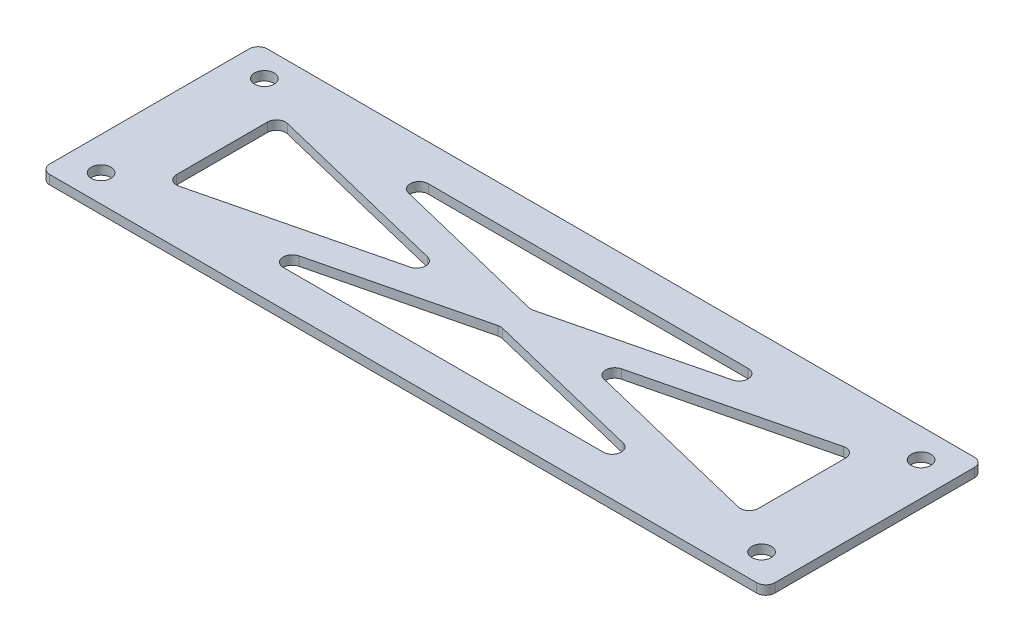
SolidWorks part; units mm, degrees
ref_plane "Front Plane" through (0, 0, 0) normal (0, 0, 1) x (1, 0, 0)
ref_plane "Top Plane" through (0, 0, 0) normal (0, 1, 0) x (1, 0, 0)
ref_plane "Right Plane" through (0, 0, 0) normal (1, 0, 0) x (0, 0, -1)
sketch "Sketch1" plane through (0, 0, 0) normal (0, 1, 0) x (1, 0, 0)
  line L0 (-115.35, 0) -> (115.35, 0) construction
  line L1 (-127, -38.1) -> (127, -38.1)
  line L2 (-127, -38.1) -> (-127, 38.1)
  line L3 (-127, 38.1) -> (127, 38.1)
  line L4 (127, -38.1) -> (127, 38.1)
  line L5 (-127, -38.1) -> (127, 38.1) construction
  line L6 (-127, 38.1) -> (127, -38.1) construction
  line L7 (-115.35, 28.575) -> (-115.35, -28.575) construction
  line L8 (115.35, 27.94) -> (115.35, -27.94) construction
  circle A3 centre (-115.35, 28.575) radius 3.429
  circle A4 centre (-115.35, -28.575) radius 3.429
  circle A5 centre (115.35, 27.94) radius 3.429
  circle A6 centre (115.35, -27.94) radius 3.429
  point P0 (0, 0)
  point P8 (0, 0)
  point P13 (-115.35, 0)
  point P18 (115.35, 0)
  point P21 (0, 0)
  dimension "D4" = 57.15
  dimension "D5" = 6.858
  dimension "D1" = 254
  dimension "D2" = 76.2
  dimension "D3" = 230.7
  dimension "D6" = 55.88
extrude "Boss-Extrude1" add sketch "Sketch1" along normal blind 3.175
fillet "Fillet1" radius 3.175 4 edges at (127, 1.5875, -38.1) (127, 1.5875, 38.1) (-127, 1.5875, -38.1) (-127, 1.5875, 38.1)
sketch "Sketch2" plane through (0, 3.175, 0) normal (0, 1, 0) x (1, 0, 0)
  line L0 (-101.6, 25.4) -> (-101.6, -25.4)
  line L1 (101.6, -25.4) -> (101.6, 25.4)
  line L12 (-115.35, 28.575) -> (115.35, -27.94) construction
  line L13 (-115.35, -28.575) -> (115.35, 27.94) construction
  line L14 (-116.5587, 23.6409) -> (114.1413, -32.8741)
  line L15 (-114.1413, -33.5091) -> (116.5587, 23.0059)
  line L16 (-114.3, 25.4) -> (-114.3, -25.4)
  line L17 (-114.3, -25.4) -> (114.3, -25.4)
  line L18 (114.3, -25.4) -> (114.3, 25.4)
  line L19 (114.3, 25.4) -> (-114.3, 25.4)
  line L20 (-114.3, 25.4) -> (-114.3, -25.4)
  line L21 (-114.3, -25.4) -> (114.3, -25.4)
  line L22 (114.3, -25.4) -> (114.3, 25.4)
  line L23 (114.3, 25.4) -> (-114.3, 25.4)
  line L24 (-114.1413, 33.5091) -> (116.5587, -23.0059)
  line L25 (-116.5587, -23.6409) -> (114.1413, 32.8741)
  circle A18 centre (-115.35, 28.575) radius 16.129
  circle A19 centre (-115.35, 28.575) radius 16.129
  circle A24 centre (115.35, 27.94) radius 16.129
  circle A25 centre (115.35, 27.94) radius 16.129
  circle A27 centre (115.35, -27.94) radius 16.129
  circle A28 centre (115.35, -27.94) radius 16.129
  circle A30 centre (-115.35, -28.575) radius 16.129
  circle A31 centre (-115.35, -28.575) radius 16.129
  dimension "D7" = 5.08
  dimension "D1" = 12.7
  dimension "D2" = 12.7
  dimension "D4" = 12.7
  dimension "D5" = 12.7
  dimension "D6" = 12.7
  dimension "D8" = 5.08
  dimension "D9" = 12.7
extrude "Cut-Extrude1" cut sketch "Sketch2" against normal through all contours L0 L25 L14 | L25 L23 L24 | L15 L24 L1 | L15 L21 L14 region at (-74.4181, 3.175, 0) region at (1.2961, 3.175, -18.6767) region at (1.2961, 3.175, 18.6767) region at (75.2821, 3.175, 0)
fillet "Fillet3" radius 3.175 12 edges at (22.6463, 1.5875, 0) (83.6312, 1.5875, -25.4) (83.6312, 1.5875, 25.4) (-81.0391, 1.5875, 25.4) (-81.0391, 1.5875, -25.4) (-20.0542, 1.5875, 0) (101.6, 1.5875, -19.3414) (101.6, 1.5875, 19.3414) (-101.6, 1.5875, 19.9764) (-101.6, 1.5875, -19.9764) (1.2961, 1.5875, -5.2302) (1.2961, 1.5875, 5.2302)
